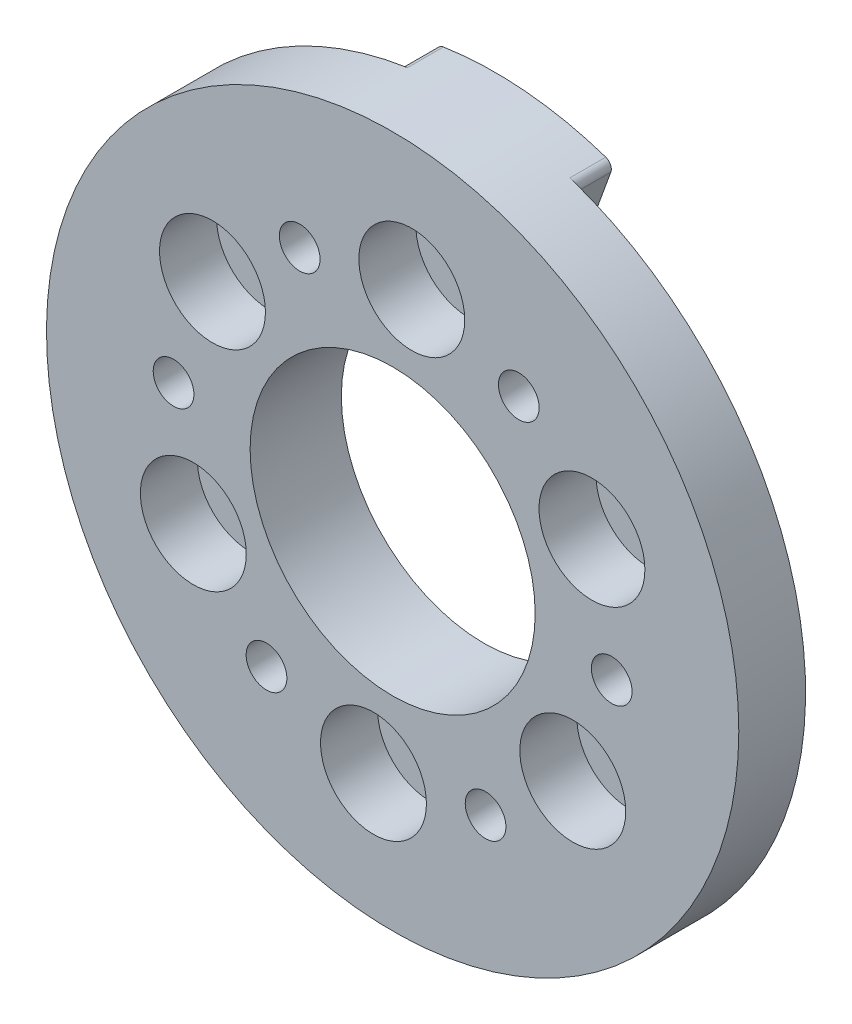
SolidWorks part; units mm, degrees
ref_plane "前视基准面" through (0, 0, 0) normal (0, 0, 1) x (1, 0, 0)
ref_plane "上视基准面" through (0, 0, 0) normal (0, 1, 0) x (1, 0, 0)
ref_plane "右视基准面" through (0, 0, 0) normal (1, 0, 0) x (0, 0, -1)
ref_plane "基准面1" through (0, 0, 0) normal (0.9397, -0.342, 0) x (0.342, 0.9397, 0)
sketch "草图1" plane through (0, 0, 0) normal (0.9397, -0.342, 0) x (0.342, 0.9397, 0)
  line L0 (21.25, -0.7) -> (21.25, 0)
  line L1 (21.25, 0) -> (17.5, 0)
  line L2 (17.5, 0) -> (17.5, -0.7)
  line L3 (17.5, -0.7) -> (21.25, -0.7)
  line L4 (0, 0) -> (0, -0.7) construction
revolve "旋转1" add sketch "草图1" angle 30 about L4 reverse direction yes
sketch "草图2" plane through (0, 0, 0) normal (0, 0, 1) x (1, 0, 0)
  line L0 (-3.0388, 17.2341) -> (-3.69, 20.9272)
  line L1 (7.2679, 19.9685) -> (5.9854, 16.4446)
  arc A0 (-5.9351, 16.4628) -> (-3.0388, 17.2341) centre (-4.5035, 16.9106) ccw
  arc A1 (-3.69, 20.9272) -> (7.2679, 19.9685) centre (0, 0) cw
  arc A2 (5.9854, 16.4446) -> (8.7037, 15.1821) centre (7.3716, 15.8717) ccw
  arc A3 (8.7037, 15.1821) -> (-5.9351, 16.4628) centre (0, 0) cw
extrude "凸台-拉伸1" add sketch "草图2" along normal blind 1.5
ref_plane "基准面2" through (0, 0, 1.5) normal (0, 0, -1) x (-1, 0, 0)
sketch "草图3" plane through (0, 0, 1.5) normal (0, 0, -1) x (-1, 0, 0)
  circle A0 centre (0, 0) radius 21.25
extrude "凸台-拉伸2" add sketch "草图3" against normal blind 4.1
hole_wizard "Ø2.5 (2.5) 直径孔1" positions "草图5" profile "草图4" hole size "Ø2.5" standard "ANSI Metric"
sketch "草图5" plane through (0, 0, 0) normal (0, 0, -1) x (-1, 0, 0)
  point P0 (13.4486, 1.1766)
  point P1 (7.7433, -11.0586)
  point P2 (-5.7053, -12.2352)
  point P3 (-13.4486, -1.1766)
  point P4 (-7.7433, 11.0586)
  point P5 (5.7053, 12.2352)
sketch "草图4" plane through (-13.4486, 1.1766, 0) normal (1, 0, 0) x (0, 1, 0)
  line L0 (0, 0) -> (0, 5.6)
  line L1 (0, 5.6) -> (1.25, 5.6)
  line L2 (1.25, 5.6) -> (1.25, 0)
  line L5 (1.25, 0) -> (0, 0)
  line L11 (0, -6.35) -> (0, 107.95) construction
  dimension "通孔孔直径" = 2.5
  dimension "通孔孔深度" = 5.6
hole_wizard "Ø17.5 (17.5) 直径孔1" positions "草图7" profile "草图6" hole size "Ø17.5" standard "ANSI Metric"
sketch "草图7" plane through (0, 0, 5.6) normal (0, 0, 1) x (1, 0, 0)
  point P0 (0, 0)
sketch "草图6" plane through (0, 0, 5.6) normal (1, 0, 0) x (0, -1, 0)
  line L0 (0, 0) -> (0, 6.3)
  line L1 (0, 6.3) -> (8.75, 6.3)
  line L2 (8.75, 6.3) -> (8.75, 0)
  line L5 (8.75, 0) -> (0, 0)
  line L11 (0, -6.35) -> (0, 107.95) construction
  dimension "通孔孔直径" = 17.5
  dimension "通孔孔深度" = 6.3
hole_wizard "M3 六角头机械螺钉的柱形沉头孔1" positions "草图9" profile "草图8" counterbore size "M3" standard "ANSI Metric"
sketch "草图9" plane through (0, 0, 5.6) normal (0, 0, 1) x (1, 0, 0)
  point P0 (12.2352, 5.7053)
  point P1 (1.1766, 13.4486)
  point P2 (-11.0586, 7.7433)
  point P3 (-12.2352, -5.7053)
  point P4 (-1.1766, -13.4486)
  point P5 (11.0586, -7.7433)
sketch "草图8" plane through (12.2352, 5.7053, 5.6) normal (1, 0, 0) x (0, -1, 0)
  line L0 (0, 0) -> (0, 6.3)
  line L1 (0, 6.3) -> (1.7, 6.3)
  line L3 (1.7, 6.3) -> (1.7, 3.5)
  line L4 (1.7, 3.5) -> (3.25, 3.5)
  line L5 (3.25, 3.5) -> (3.25, 0)
  line L7 (3.25, 0) -> (0, 0)
  line L11 (0, -6.35) -> (0, 107.95) construction
  dimension "通孔孔直径" = 3.4
  dimension "通孔孔深度" = 6.3
  dimension "柱形沉头孔直径" = 6.5
  dimension "柱形沉头孔深度" = 3.5
fillet "圆角1" radius 0.5 4 edges at (-3.69, 20.9272, 0.4) (-3.0388, 17.2341, -0.35) (7.2679, 19.9685, 0.4) (5.9854, 16.4446, -0.35) tangent propagation no
fillet "圆角2" radius 1 2 edges at (-5.9351, 16.4628, 0.75) (8.7037, 15.1821, 0.75) tangent propagation no
